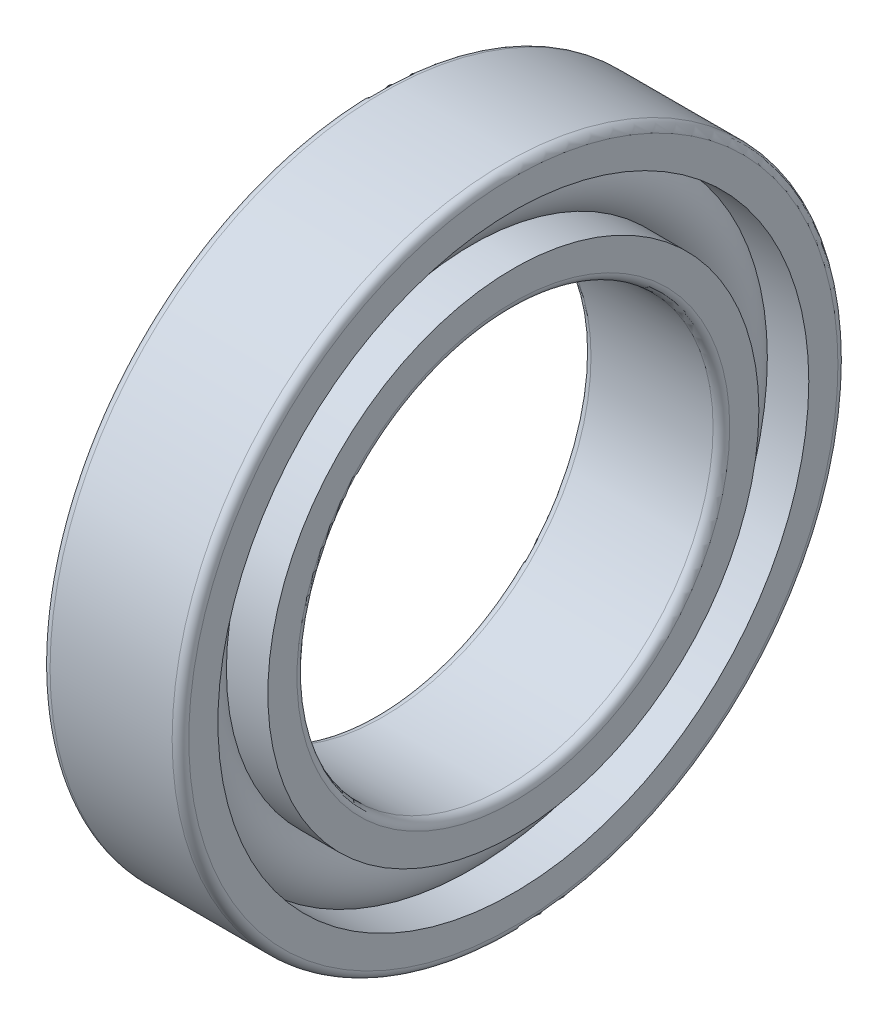
SolidWorks part; units mm, degrees
ref_plane "Plane1" through (0, 0, 0) normal (0, 0, 1) x (1, 0, 0)
ref_plane "Plane2" through (0, 0, 0) normal (0, 1, 0) x (1, 0, 0)
ref_plane "Plane3" through (0, 0, 0) normal (1, 0, 0) x (0, 0, -1)
sketch "Clipboard" plane through (0, 0, 0) normal (0, 0, 1) x (1, 0, 0)
  line L0 (-10, 0) -> (10, 0) construction
  line L1 (0, 0) -> (22.3471, -0.7804)
  line L2 (0, 0) -> (9.7441, 0.3403)
  line L3 (0, 0) -> (22.3471, -0.7804)
  line L4 (0, 0) -> (-22.3573, -0.3902)
  dimension "BallCLRad" = 9.75
  dimension "Count" = 2
  dimension "Show_count" = 2
  dimension "Max_count" = 2
  dimension "Min_count" = 1
sketch "CagSpiSke" plane through (0, 0, 0) normal (0, 0, 1) x (1, 0, 0)
  line L0 (0.135, 9.525) -> (0.135, 9.975)
  line L1 (0.135, 9.975) -> (-0.135, 9.975)
  line L2 (-0.135, 9.975) -> (-0.135, 9.525)
  line L3 (-0.135, 9.525) -> (0.135, 9.525)
  line L4 (-20.6375, 0) -> (20.6375, 0) construction
  line L5 (0, 0) -> (0, 23.7692) construction
  dimension "Thickness" = 0.27
  dimension "OD" = 19.95
  dimension "ID" = 19.05
revolve "CageSpine" add sketch "CagSpiSke" angle 0.001 about L4 reverse direction yes
ref_axis "Axis1" through (-50, 0, 0) along (1, 0, 0)
sketch "CagBalSke" plane through (0, 0, 0) normal (0, 0, 1) x (1, 0, 0)
  line L0 (-1.485, 9.75) -> (1.485, 9.75)
  line L1 (-1.905, 9.75) -> (1.905, 9.75) construction
  line L2 (-10, 0) -> (10, 0) construction
  line L3 (0, 0) -> (0, 24) construction
  arc A0 (1.485, 9.75) -> (-1.485, 9.75) centre (0, 9.75) cw
  dimension "CageWallOD" = 2.97
  dimension "BallCLRad" = 9.75
revolve "CageBall" [suppressed] add sketch "CagBalSke" angle 360 about L1 reverse direction yes
pattern_circular "CageBalls" [suppressed] count 2 every 180 about axis through (-50, 0, 0) along (1, 0, 0)
sketch "CagTrmODSke" plane through (0, 0, 0) normal (0, 0, 1) x (1, 0, 0)
  line L0 (1.486, 9.975) -> (1.486, 11.236)
  line L1 (1.486, 11.236) -> (-1.486, 11.236)
  line L2 (-1.486, 11.236) -> (-1.486, 9.975)
  line L3 (-1.486, 9.975) -> (1.486, 9.975)
  line L4 (-20.6375, 0) -> (20.6375, 0) construction
  line L5 (0, 0) -> (0, 25) construction
  dimension "Width" = 2.972
  dimension "ID" = 19.95
  dimension "OD" = 22.472
revolve "CageTrimOD" [suppressed] cut sketch "CagTrmODSke" angle 360 about L4 reverse direction yes
sketch "CagTrmIDSke" plane through (0, 0, 0) normal (0, 0, 1) x (1, 0, 0)
  line L0 (1.486, 8.266) -> (1.486, 9.525)
  line L1 (1.486, 9.525) -> (-1.486, 9.525)
  line L2 (-1.486, 9.525) -> (-1.486, 8.266)
  line L3 (-1.486, 8.266) -> (1.486, 8.266)
  line L4 (-20.6375, 0) -> (20.6375, 0) construction
  line L5 (0, 0) -> (0, 25) construction
  dimension "ID" = 16.532
  dimension "OD" = 19.05
  dimension "Width" = 2.972
revolve "CageTrimID" [suppressed] cut sketch "CagTrmIDSke" angle 360 about L4 reverse direction yes
sketch "BalSimSke" plane through (0, 0, 0) normal (0, 0, 1) x (1, 0, 0)
  line L0 (-10, 0) -> (10, 0) construction
  line L1 (-10, 9.75) -> (10, 9.75) construction
  line L2 (0, 0) -> (0, 23) construction
  circle A0 centre (0, 9.75) radius 1.35
  dimension "Ball_diameter" = 2.7
  dimension "BallCLRad" = 9.75
revolve "BallsSimplified" add sketch "BalSimSke" angle 360 about L0
sketch "BalDetSke" plane through (0, 0, 0) normal (0, 0, 1) x (1, 0, 0)
  line L0 (-1.35, 9.75) -> (1.35, 9.75)
  line L1 (-1.905, 9.75) -> (1.905, 9.75) construction
  line L2 (0, 0) -> (0, 25) construction
  arc A0 (1.35, 9.75) -> (-1.35, 9.75) centre (0, 9.75) cw
  dimension "Ball_diameter" = 2.7
  dimension "BallCLRad" = 9.75
revolve "BallDetailed" [suppressed] add sketch "BalDetSke" angle 360 about L1 reverse direction yes
sketch "InnRacSke" plane through (0, 0, 0) normal (0, 0, 1) x (1, 0, 0)
  line L0 (-0.9724, 8.85) -> (-2.5, 8.85)
  line L1 (-2.5, 8.85) -> (-2.5, 7.8)
  line L2 (-2.2, 7.5) -> (2.2, 7.5)
  line L3 (2.5, 7.8) -> (2.5, 8.85)
  line L4 (2.5, 8.85) -> (0.9724, 8.85)
  line L5 (-20.6375, 0) -> (20.6375, 0) construction
  line L6 (0, 0) -> (0, 30) construction
  arc A0 (-2.5, 7.8) -> (-2.2, 7.5) centre (-2.2, 7.8) ccw
  arc A1 (2.2, 7.5) -> (2.5, 7.8) centre (2.2, 7.8) ccw
  arc A2 (0.9724, 8.85) -> (-0.9724, 8.85) centre (0, 9.75) cw
  dimension "Fillet_radius" = 0.3
  dimension "Ball_diameter" = 2.65
  dimension "ID" = 15
  dimension "OD" = 17.7
  dimension "Width" = 5
  dimension "BallCLRad" = 9.75
revolve "InnerRace" add sketch "InnRacSke" angle 360 about L5 reverse direction yes
sketch "OutRacSke" plane through (0, 0, 0) normal (0, 0, 1) x (1, 0, 0)
  line L0 (-0.9724, 10.65) -> (-2.5, 10.65)
  line L1 (-2.5, 10.65) -> (-2.5, 11.7)
  line L2 (-2.2, 12) -> (2.2, 12)
  line L3 (2.5, 11.7) -> (2.5, 10.65)
  line L4 (2.5, 10.65) -> (0.9724, 10.65)
  line L5 (-20.6375, 0) -> (20.6375, 0) construction
  line L6 (0, 0) -> (0, 30) construction
  arc A0 (-2.5, 11.7) -> (-2.2, 12) centre (-2.2, 11.7) cw
  arc A1 (2.2, 12) -> (2.5, 11.7) centre (2.2, 11.7) cw
  arc A2 (0.9724, 10.65) -> (-0.9724, 10.65) centre (0, 9.75) ccw
  dimension "Fillet_radius" = 0.3
  dimension "Ball_diameter" = 2.65
  dimension "OD" = 24
  dimension "ID" = 21.3
  dimension "Width" = 5
  dimension "BallCLRad" = 9.75
revolve "OuterRace" add sketch "OutRacSke" angle 360 about L5 reverse direction yes
pattern_circular "BallsDetailed" [suppressed] count 2 every 180 about axis through (-50, 0, 0) along (1, 0, 0)
equation "\"BallCLRad@Clipboard\" = ( \"OD@OutRacSke\" + \"ID@InnRacSke\" ) / 4"
equation "\"BallCLRad@BalSimSke\" = \"BallCLRad@Clipboard\""
equation "\"BallCLRad@BalDetSke\" = \"BallCLRad@Clipboard\""
equation "\"BallCLRad@InnRacSke\" = \"BallCLRad@Clipboard\""
equation "\"BallCLRad@OutRacSke\" = \"BallCLRad@Clipboard\""
equation "\"Ball_diameter@InnRacSke\" = \"Ball_diameter@BalDetSke\" - 0.05"
equation "\"Ball_diameter@OutRacSke\" = \"Ball_diameter@BalDetSke\" - 0.05"
equation "\"Ball_diameter@BalSimSke\" = \"Ball_diameter@BalDetSke\""
equation "\"Width@OutRacSke\" = \"Width@InnRacSke\""
equation "\"Fillet_radius@OutRacSke\" = \"Fillet_radius@InnRacSke\""
equation "\"Max_count@Clipboard\" = int( 3.14159265 / atn(( \"Ball_diameter@BalDetSke\" / 2) / sqr( \"BallCLRad@Clipboard\"  *  \"BallCLRad@Clipboard\" - ( \"Ball_diameter@BalDetSke\" / 2) *  ( \"Ball_diameter@BalDetSke\" / 2))))"
equation "\"Max_count@Clipboard\" = ((sgn( \"Max_count@Clipboard\" - \"Count@Clipboard\" )-1)*( \"Max_count@Clipboard\" - \"Count@Clipboard\" ))/-2+ \"Count@Clipboard\""
equation "\"Count@BallsDetailed\" = int( \"Show_count@Clipboard\" ) "
equation "\"Count@BallsDetailed\" = ((sgn( \"Count@BallsDetailed\" - \"Max_count@Clipboard\" )-1)*( \"Count@BallsDetailed\" - \"Max_count@Clipboard\" ))/-2+ \"Max_count@Clipboard\""
equation "\"Count@BallsDetailed\" = ((sgn( \"Count@BallsDetailed\" - \"Min_count@Clipboard\" )+1)*( \"Count@BallsDetailed\" - \"Min_count@Clipboard\"))/2 +\"Min_count@Clipboard\""
equation "\"Angle@BallsDetailed\" = 360.0 / \"Max_count@Clipboard\""
equation "\"BallCLRad@CagBalSke\" = \"BallCLRad@Clipboard\""
equation "\"Count@CageBalls\" = \"Count@BallsDetailed\""
equation "\"Angle@CageBalls\" = \"Angle@BallsDetailed\""
equation "\"Angle@CageSpine\" =  \"Angle@CageBalls\" * ( \"Count@CageBalls\" -1 + int( \"Count@CageBalls\" / \"Max_count@Clipboard\" ) )  + 0.001 -  int( \"Count@CageBalls\" / \"Max_count@Clipboard\" ) * 0.001"
equation "\"Angle@CageSpine\" =  \"Angle@CageSpine\" * int( \"Min_count@Clipboard\" / 2) + int(1 / \"Min_count@Clipboard\")  * 0.001"
equation "\"CageWallOD@CagBalSke\" =  \"Ball_diameter@BalDetSke\" * 1.1"
equation "\"Thickness@CagSpiSke\" =  \"Ball_diameter@BalDetSke\" * 0.1"
equation "\"OD@CagTrmODSke\" = \"BallCLRad@Clipboard\" * 2 + \"CageWallOD@CagBalSke\" + 0.002"
equation "\"ID@CagTrmODSke\" = \"BallCLRad@Clipboard\" * 2 + \"Ball_diameter@BalDetSke\" / 6"
equation "\"OD@CagTrmIDSke\" = \"BallCLRad@Clipboard\" * 2 - \"Ball_diameter@BalDetSke\" / 6"
equation "\"ID@CagTrmIDSke\" = \"BallCLRad@Clipboard\" * 2 - \"CageWallOD@CagBalSke\" + 0.002"
equation "\"OD@CagSpiSke\" = \"ID@CagTrmODSke\""
equation "\"ID@CagSpiSke\" = \"OD@CagTrmIDSke\""
equation "\"Width@CagTrmODSke\" = \"CageWallOD@CagBalSke\" + 0.002"
equation "\"Width@CagTrmIDSke\" = \"CageWallOD@CagBalSke\" + 0.002"
